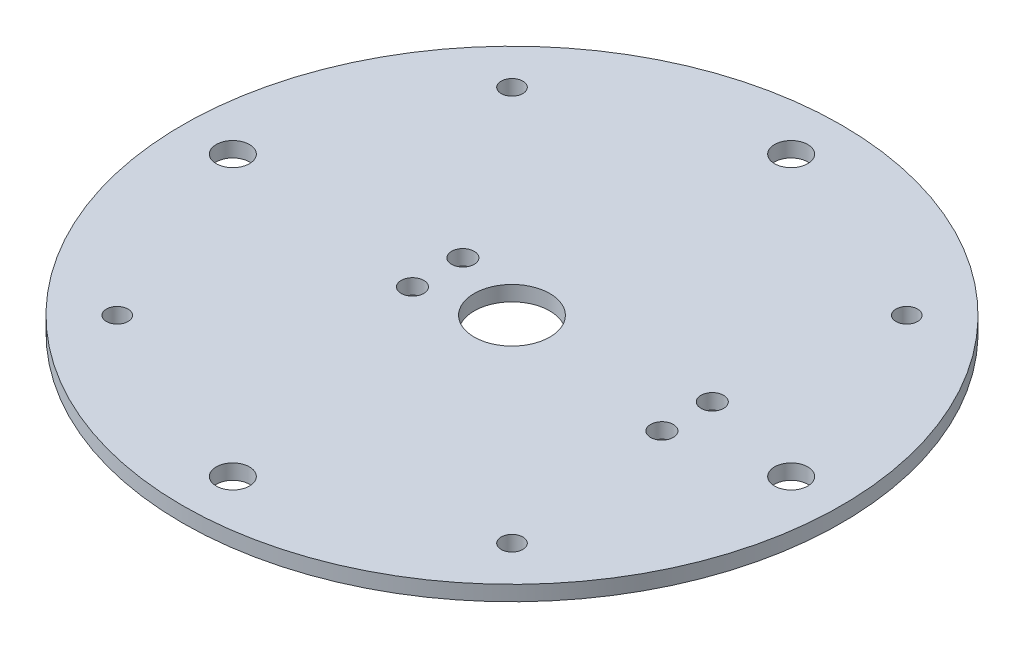
SolidWorks part; units mm, degrees
ref_plane "Front Plane" through (0, 0, 0) normal (0, 0, 1) x (1, 0, 0)
ref_plane "Top Plane" through (0, 0, 0) normal (0, 1, 0) x (1, 0, 0)
ref_plane "Right Plane" through (0, 0, 0) normal (1, 0, 0) x (0, 0, -1)
sketch "Sketch1" plane through (0, 0, 0) normal (0, 1, 0) x (1, 0, 0)
  circle A0 centre (0, 0) radius 65.4
  dimension "Diameter" = 130.8
extrude "Boss-Extrude1" add sketch "Sketch1" along normal mid plane 3
hole_wizard "M6 Clearance Hole1" positions "Sketch8" profile "Sketch9" hole size "M6" standard "ANSI Metric" end condition up to next
sketch "Sketch8" plane through (0, 1.5, 0) normal (0, 1, 0) x (1, 0, 0)
  line L0 (0, 0) -> (55.4, 0) construction
  point P0 (55.4, 0)
  dimension "ThreadedHoleDistance" = 55.4
sketch "Sketch9" plane through (55.4, 1.5, 0) normal (1, 0, 0) x (0, 0, 1)
  line L0 (0, 0) -> (0, 3)
  line L1 (0, 3) -> (3.3, 3)
  line L2 (3.3, 3) -> (3.3, 0)
  line L5 (3.3, 0) -> (0, 0)
  line L11 (0, -6.35) -> (0, 107.95) construction
  dimension "Thru Hole Dia." = 6.6
  dimension "Thru Hole Depth" = 3
pattern_circular "CirPattern2" count 4 over 360 about axis through (0, 1.5, 0) along (0, -1, 0) of "M6 Clearance Hole1" reverse direction yes
sketch "Sketch5" plane through (0, 1.5, 0) normal (0, 1, 0) x (1, 0, 0)
  line L0 (0, 0) -> (65.4, 0) construction
  line L2 (0, 0) -> (39.1737, 39.1737) construction
  circle A0 centre (0, 0) radius 65.4 construction
  dimension "D1" = 45
  dimension " NoseShellHoleRadius" = 55.4
hole_wizard "M4 Clearance Hole1" positions "Sketch6" profile "Sketch7" hole size "M4" standard "ANSI Metric" end condition up to next
sketch "Sketch6" plane through (0, 1.5, 0) normal (0, 1, 0) x (1, 0, 0)
  point P0 (39.1737, 39.1737)
sketch "Sketch7" plane through (39.1737, 1.5, -39.1737) normal (1, 0, 0) x (0, 0, 1)
  line L0 (0, 0) -> (0, 3)
  line L1 (0, 3) -> (2.15, 3)
  line L2 (2.15, 3) -> (2.15, 0)
  line L5 (2.15, 0) -> (0, 0)
  line L11 (0, -6.35) -> (0, 107.95) construction
  dimension "Thru Hole Dia." = 4.3
  dimension "Thru Hole Depth" = 3
pattern_circular "CirPattern1" count 4 over 360 about axis through (0, 1.5, 0) along (0, -1, 0) of "M4 Clearance Hole1" reverse direction yes
sketch "Sketch10" plane through (0, 1.5, 0) normal (0, 1, 0) x (1, 0, 0)
  circle A0 centre (0, 0) radius 7.5
  dimension "D1" = 15
extrude "Cut-Extrude1" cut sketch "Sketch10" against normal through all
sketch "Sketch11" plane through (0, -1.5, 0) normal (0, -1, 0) x (1, 0, 0)
  circle A0 centre (-14.75, -5) radius 2.25
  arc A1 (-16.7656, -6) -> (-16.7656, -4) centre (-14.75, -5) ccw construction
  circle A2 centre (-14.75, 5) radius 2.25
  circle A3 centre (34.75, -5) radius 2.25
  circle A4 centre (34.75, 5) radius 2.25
  arc A5 (-16.7656, 4) -> (-16.7656, 6) centre (-14.75, 5) ccw construction
  arc A6 (36.7656, 6) -> (36.7656, 4) centre (34.75, 5) ccw construction
  arc A7 (36.7656, -4) -> (36.7656, -6) centre (34.75, -5) ccw construction
extrude "Cut-Extrude2" cut sketch "Sketch11" against normal through all
